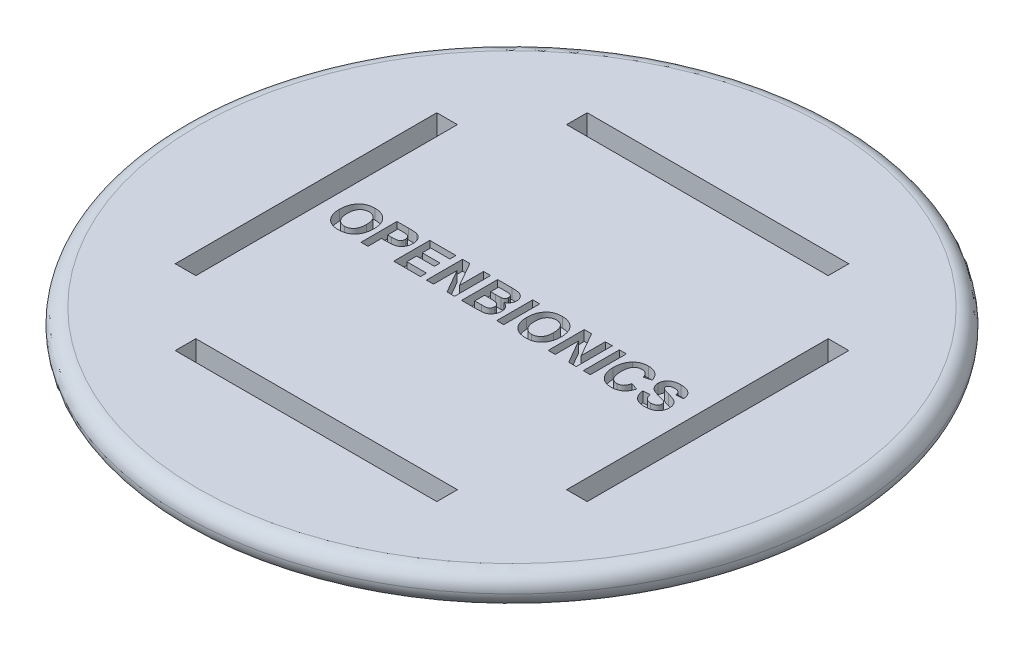
SolidWorks part; units mm, degrees
ref_plane "Front Plane" through (0, 0, 0) normal (0, 0, 1) x (1, 0, 0)
ref_plane "Top Plane" through (0, 0, 0) normal (0, 1, 0) x (1, 0, 0)
ref_plane "Right Plane" through (0, 0, 0) normal (1, 0, 0) x (0, 0, -1)
sketch "Sketch1" plane through (0, 0, 0) normal (0, 1, 0) x (1, 0, 0)
  line L3 (20, 0) -> (20, -12.7)
  line L4 (0, -20) -> (12.7, -20)
  line L5 (12.7, -20) -> (12.7, -18)
  line L6 (12.7, -18) -> (-12.7, -18)
  line L7 (-12.7, -18) -> (-12.7, -20)
  line L8 (-12.7, -20) -> (0, -20)
  line L9 (-12.7, 20) -> (0, 20)
  line L10 (-12.7, 18) -> (-12.7, 20)
  line L11 (12.7, 18) -> (-12.7, 18)
  line L12 (12.7, 20) -> (12.7, 18)
  line L13 (0, 20) -> (12.7, 20)
  line L15 (-18, 0) -> (-18, 12.7)
  line L16 (-18, 12.7) -> (-20, 12.7)
  line L17 (-20, 12.7) -> (-20, -12.7)
  line L18 (-20, -12.7) -> (-18, -12.7)
  line L19 (-18, -12.7) -> (-18, 0)
  line L20 (18, -12.7) -> (18, 0)
  line L21 (20, -12.7) -> (18, -12.7)
  line L22 (20, 12.7) -> (20, 0)
  line L23 (18, 12.7) -> (20, 12.7)
  line L24 (18, 0) -> (18, 12.7)
  circle A0 centre (0, 0) radius 32
extrude "Boss-Extrude1" add sketch "Sketch1" along normal blind 3
fillet "Fillet1" radius 1.5 2 edges at (0, 3, 32) (0, 0, 32)
sketch "Sketch2" plane through (0, 3, 0) normal (0, 1, 0) x (1, 0, 0)
  text T0 "<b>OPENBIONICS</b>" font "Arial Narrow" height 3.5
extrude "Cut-Extrude16" cut sketch "Sketch2" against normal blind 1
